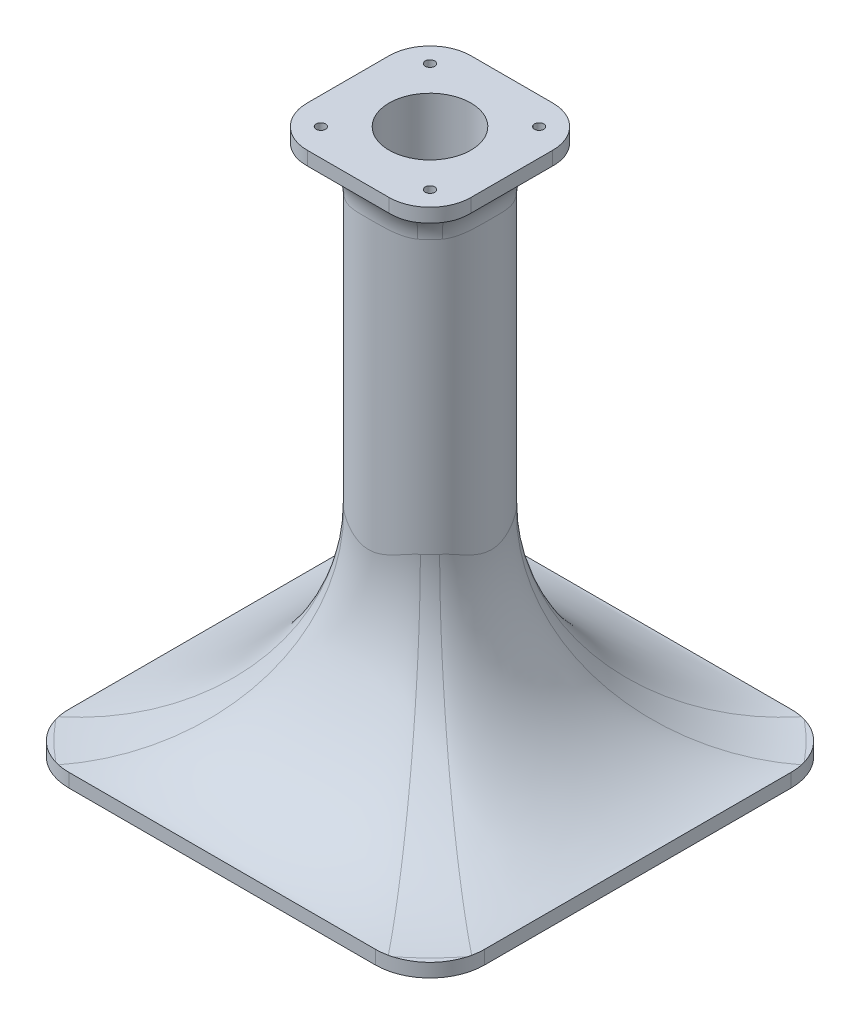
SolidWorks part; units mm, degrees
ref_plane "Front Plane" through (0, 0, 0) normal (0, 0, 1) x (1, 0, 0)
ref_plane "Top Plane" through (0, 0, 0) normal (0, 1, 0) x (1, 0, 0)
ref_plane "Right Plane" through (0, 0, 0) normal (1, 0, 0) x (0, 0, -1)
sketch "Sketch1" plane through (0, 0, 0) normal (0, 1, 0) x (1, 0, 0)
  circle A0 centre (0, 0) radius 22.5
  circle A1 centre (0, 0) radius 12.5
  dimension "D1" = 45
  dimension "D2" = 25
extrude "Boss-Extrude1" add sketch "Sketch1" along normal blind 200 contours A0 A1 | A1 region at (-21.8636, 0, 0)
sketch "Sketch2" plane through (0, 0, 0) normal (0, 1, 0) x (1, 0, 0)
  line L1 (-76.2, -76.2) -> (76.2, -76.2)
  line L2 (-76.2, -76.2) -> (-76.2, 76.2)
  line L3 (-76.2, 76.2) -> (76.2, 76.2)
  line L4 (76.2, -76.2) -> (76.2, 76.2)
  line L5 (-76.2, -76.2) -> (76.2, 76.2) construction
  line L6 (-76.2, 76.2) -> (76.2, -76.2) construction
  point P0 (0, 0)
  dimension "D1" = 152.4
  dimension "D2" = 152.4
extrude "Boss-Extrude3" add sketch "Sketch2" along normal blind 5
fillet "Fillet3" radius 75 1 edges at (0, 5, -22.5) tangent propagation no
sketch "Sketch4" plane through (0, 0, 0) normal (0, -1, 0) x (1, 0, 0)
  circle A0 centre (0, 0) radius 15
extrude "Cut-Extrude1" cut sketch "Sketch4" against normal blind 200
fillet "Fillet4" radius 20 4 edges at (-76.2, 2.5, 76.2) (76.2, 2.5, 76.2) (-76.2, 2.5, -76.2) (76.2, 2.5, -76.2)
sketch "Sketch5" plane through (0, 0, 0) normal (0, 1, 0) x (1, 0, 0)
  line L0 (-76.2, 76.2) -> (76.2, -76.2) construction
  line L1 (76.2, 76.2) -> (-76.2, -76.2) construction
  line L2 (-61.2, 61.2) -> (-61.2, -61.2) construction
  line L3 (-61.2, -61.2) -> (61.2, -61.2) construction
  line L4 (61.2, -61.2) -> (61.2, 61.2) construction
  line L5 (61.2, 61.2) -> (-61.2, 61.2) construction
  line L6 (-76.2, 56.2) -> (-76.2, -56.2) construction
  line L7 (-76.2, 76.2) -> (76.2, 76.2)
  line L8 (-76.2, 76.2) -> (-76.2, -76.2)
  line L9 (-76.2, -76.2) -> (76.2, -76.2)
  line L10 (76.2, 76.2) -> (76.2, -76.2)
  line L11 (-76.2, 76.2) -> (76.2, -76.2) construction
  line L12 (-76.2, -76.2) -> (76.2, 76.2) construction
  line L13 (76.2, -56.2) -> (76.2, 56.2) construction
  line L14 (56.2, 76.2) -> (-56.2, 76.2) construction
  line L15 (-56.2, -76.2) -> (56.2, -76.2) construction
  circle A4 centre (-61.2, 61.2) radius 1.7
  circle A5 centre (61.2, 61.2) radius 1.7
  circle A6 centre (61.2, -61.2) radius 1.7
  circle A7 centre (-61.2, -61.2) radius 1.7
  point P6 (0, 0)
  dimension "D1" = 3.4
  dimension "D2" = 15
sketch "Sketch6" plane through (0, 200, 0) normal (0, 1, 0) x (1, 0, 0)
  line L1 (-30, -30) -> (30, -30)
  line L2 (-30, -30) -> (-30, 30)
  line L3 (-30, 30) -> (30, 30)
  line L4 (30, -30) -> (30, 30)
  line L5 (-30, -30) -> (30, 30) construction
  line L6 (-30, 30) -> (30, -30) construction
  circle A1 centre (0, 0) radius 15
  point P0 (0, 0)
  dimension "D1" = 60
  dimension "D2" = 60
extrude "Boss-Extrude4" add sketch "Sketch6" against normal blind 5
fillet "Fillet5" radius 15 1 edges at (0, 195, -22.5)
fillet "Fillet6" radius 15 4 edges at (30, 197.5, -30) (30, 197.5, 30) (-30, 197.5, 30) (-30, 197.5, -30)
sketch "Sketch7" plane through (0, 200, 0) normal (0, 1, 0) x (1, 0, 0)
  line L0 (15, 30) -> (-15, 30) construction
  line L1 (-30, -30) -> (30, -30)
  line L2 (-30, -30) -> (-30, 30)
  line L3 (-30, 30) -> (30, 30)
  line L4 (30, -30) -> (30, 30)
  line L5 (-30, -30) -> (30, 30) construction
  line L6 (-30, 30) -> (30, -30) construction
  line L7 (-30, 15) -> (-30, -15) construction
  line L8 (-20, 20) -> (20, 20) construction
  line L9 (20, 20) -> (20, -20) construction
  line L10 (20, -20) -> (-20, -20) construction
  line L11 (-20, -20) -> (-20, 20) construction
  circle A0 centre (-20, 20) radius 1.725
  circle A1 centre (20, 20) radius 1.725
  circle A2 centre (20, -20) radius 1.725
  circle A3 centre (-20, -20) radius 1.725
  point P0 (0, 0)
  dimension "D2" = 3.45
  dimension "D1" = 10
extrude "Cut-Extrude3" cut sketch "Sketch7" against normal blind 10 contours A0 | A1 | A2 | A3 region at (-20, 200, -20) region at (20, 200, -20) region at (20, 200, 20) region at (-20, 200, 20)
